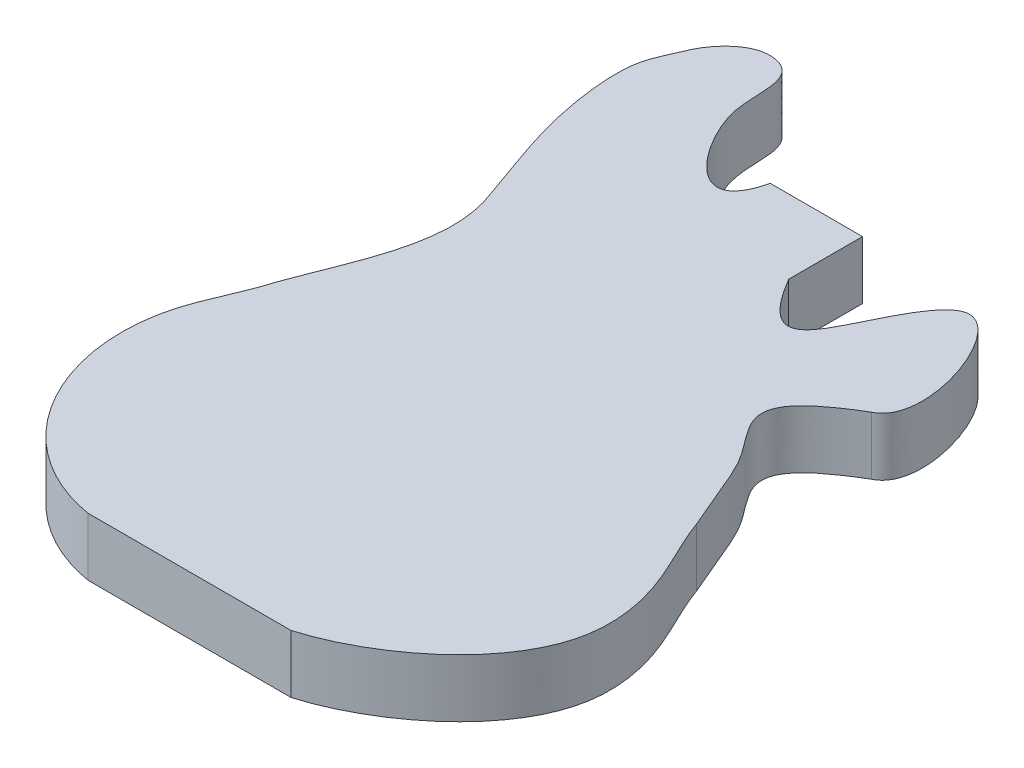
SolidWorks part; units mm, degrees
ref_plane "Front Plane" through (0, 0, 0) normal (0, 0, 1) x (1, 0, 0)
ref_plane "Top Plane" through (0, 0, 0) normal (0, 1, 0) x (1, 0, 0)
ref_plane "Right Plane" through (0, 0, 0) normal (1, 0, 0) x (0, 0, -1)
sketch "Sketch1" plane through (0, 0, 0) normal (0, 1, 0) x (1, 0, 0)
  line L0 (-31.75, 431.8) -> (31.75, 431.8)
  line L1 (-69.85, 0) -> (69.85, 0)
  line L2 (31.75, 431.8) -> (31.75, 381)
  line L3 (0, 431.8) -> (0, 0) construction
  spline S0 degree 3 poles (-69.85, 0) (-122.7459, 8.8946) (-170.3738, 68.3736) (-165.5312, 154.7593) (-147.8347, 185.8105) (-142.875, 203.2) knots 0 0 0 0 0.581043 0.783837 1 1 1 1
  spline S1 degree 3 poles (-142.875, 203.2) (-128.6398, 243.0991) (-104.4904, 285.9502) (-122.2248, 330.2) knots 0 0 0 0 1 1 1 1
  spline S2 degree 3 poles (-122.2248, 330.2) (-131.7635, 357.8566) (-146.2426, 392.3515) (-152.7726, 455.2781) (-144.5433, 471.0132) (-135.4704, 492.8612) (-120.6511, 508.7509) (-90.8297, 507.3178) (-88.3646, 481.7202) (-88.7047, 444.4419) (-43.0115, 384.6457) (-31.75, 431.8) knots 0 0 0 0 0.228271 0.373681 0.455315 0.473382 0.545352 0.564859 0.659458 0.744201 1 1 1 1
  spline S3 degree 3 poles (69.85, 0) (111.9348, 12.1111) (186.0145, 65.7497) (170.8416, 155.4983) (152.3381, 185.6263) (146.05, 203.2) knots 0 0 0 0 0.586136 0.784814 1 1 1 1
  spline S4 degree 3 poles (146.05, 203.2) (136.1599, 225.6504) (132.5896, 236.8474) (120.3836, 260.933) (109.5687, 273.3596) (96.5902, 297.0243) (109.0963, 311.9927) (139.7, 330.2) knots 0 0 0 0 0.33898 0.396393 0.554386 0.616722 1 1 1 1
  spline S5 degree 3 poles (139.7, 330.2) (166.4459, 342.892) (123.5038, 464.5308) (76.8127, 369.3895) (59.5093, 333.6668) (31.75, 381) knots 0 0 0 0 0.451982 0.679896 1 1 1 1
  point P5 (0, 412.75)
  point P7 (0, 0)
  point P10 (0, 50.8)
  point P11 (0, 101.6)
  point P12 (0, 152.4)
  point P13 (0, 177.8)
  point P15 (0, 203.2)
  point P17 (0, 254)
  point P18 (0, 279.4)
  point P19 (0, 330.2)
  point P20 (0, 406.4)
  point P21 (0, 381)
  point P22 (0, 482.6)
  point P23 (0, 508)
  point P24 (0, 457.2)
  point P25 (0, 355.6)
  point P28 (0, 0)
  point P38 (0, 422.275)
  point P49 (0, 0)
  point P53 (0, 0)
  point P55 (0, 0)
  point P57 (31.75, 381)
  dimension "D5" = 50.8
  dimension "D35" = 149.225
  dimension "D42" = 139.7
  dimension "D1" = 63.5
  dimension "D2" = 139.7
  dimension "D4" = 431.8
  dimension "D6" = 101.6
  dimension "D7" = 152.4
  dimension "D8" = 177.8
  dimension "D9" = 203.2
  dimension "D10" = 254
  dimension "D11" = 279.4
  dimension "D12" = 330.2
  dimension "D13" = 381
  dimension "D14" = 406.4
  dimension "D15" = 457.2
  dimension "D16" = 482.6
  dimension "D17" = 508
  dimension "D18" = 146.05
  dimension "D19" = 165.1
  dimension "D20" = 161.925
  dimension "D21" = 152.4
  dimension "D22" = 142.875
  dimension "D23" = 123.825
  dimension "D24" = 117.475
  dimension "D25" = 122.2248
  dimension "D26" = 139.7
  dimension "D27" = 146.05
  dimension "D28" = 149.225
  dimension "D29" = 139.7
  dimension "D30" = 107.95
  dimension "D31" = 88.9
  dimension "D32" = 85.725
  dimension "D33" = 6.35
  dimension "D34" = 53.975
  dimension "D36" = 174.625
  dimension "D37" = 168.275
  dimension "D38" = 157.1498
  dimension "D39" = 146.05
  dimension "D40" = 123.825
  dimension "D41" = 106.3498
  dimension "D43" = 355.6
  dimension "D44" = 422.275
  dimension "D45" = 146.05
  dimension "D46" = 114.3
  dimension "D47" = 82.55
  dimension "D48" = 66.675
extrude "Boss-Extrude1" add sketch "Sketch1" along normal blind 40.005
